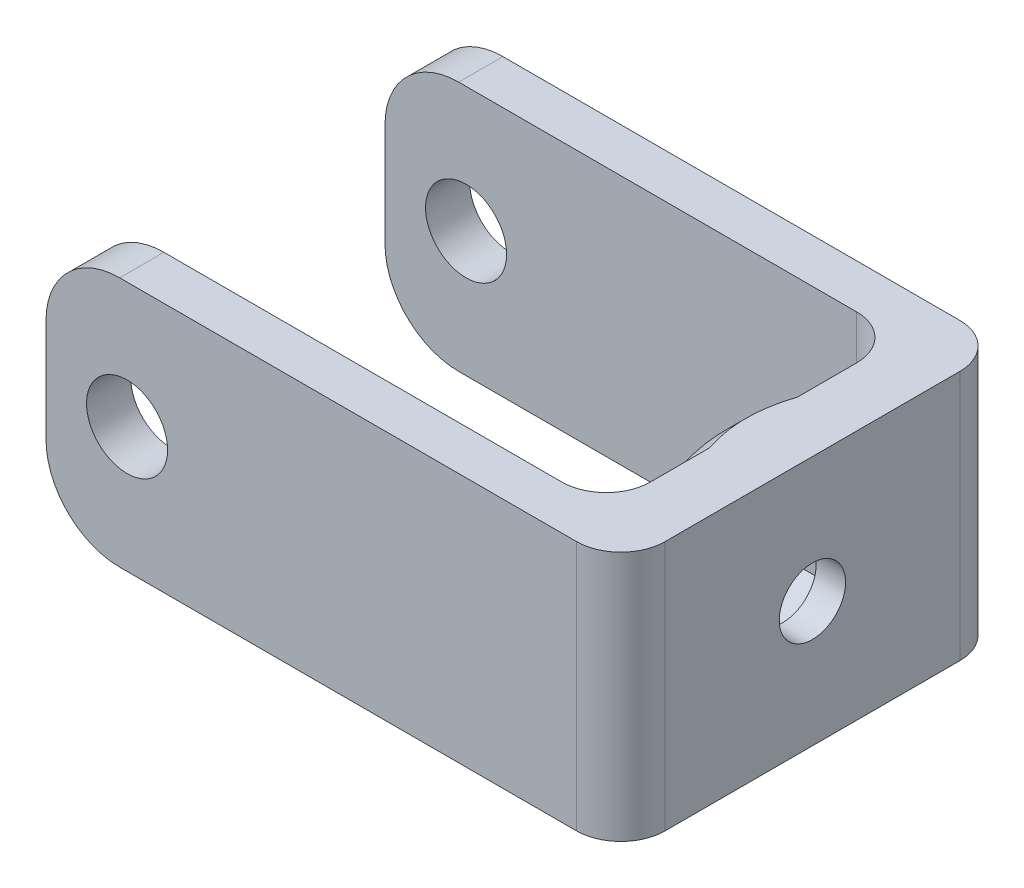
SolidWorks part; units mm, degrees
ref_plane "Front Plane" through (0, 0, 0) normal (0, 0, 1) x (1, 0, 0)
ref_plane "Top Plane" through (0, 0, 0) normal (0, 1, 0) x (1, 0, 0)
ref_plane "Right Plane" through (0, 0, 0) normal (1, 0, 0) x (0, 0, -1)
sketch "Sketch1" plane through (0, 0, 0) normal (1, 0, 0) x (0, 0, -1)
  line L1 (-13, -8.5) -> (13, -8.5)
  line L2 (-13, -8.5) -> (-13, 8.5)
  line L3 (-13, 8.5) -> (13, 8.5)
  line L4 (13, -8.5) -> (13, 8.5)
  line L5 (-13, -8.5) -> (13, 8.5) construction
  line L6 (-13, 8.5) -> (13, -8.5) construction
  point P0 (0, 0)
  dimension "D1" = 17
  dimension "D2" = 26
extrude "Boss-Extrude1" add sketch "Sketch1" along normal blind 4
sketch "Sketch2" plane through (0, 0, 0) normal (-1, 0, 0) x (0, 0, 1)
  line L0 (13, -8.5) -> (-13, -8.5) construction
  line L1 (-13, 8.5) -> (-10, 8.5)
  line L2 (-13, 8.5) -> (-13, -8.5)
  line L3 (-13, -8.5) -> (-10, -8.5)
  line L4 (-10, 8.5) -> (-10, -8.5)
  line L6 (13, 8.5) -> (10, 8.5)
  line L7 (13, 8.5) -> (13, -8.5)
  line L8 (13, -8.5) -> (10, -8.5)
  line L9 (10, 8.5) -> (10, -8.5)
  dimension "D1" = 3
  dimension "D2" = 3
extrude "Boss-Extrude2" add sketch "Sketch2" along normal blind 35
sketch "Sketch3" plane through (0, 0, 13) normal (0, 0, 1) x (1, 0, 0)
  line L1 (-35, -8.5) -> (-35, 8.5) construction
  circle A0 centre (-29.5, 0) radius 2.75
  dimension "D1" = 5.5
  dimension "D2" = 5.5
extrude "Cut-Extrude1" cut sketch "Sketch3" against normal through all
fillet "Fillet1" radius 3 4 edges at (0, 0, 10) (4, 0, 13) (4, 0, -13) (0, 0, -10)
fillet "Fillet2" radius 5 4 edges at (-35, 8.5, -11.5) (-35, -8.5, -11.5) (-35, -8.5, 11.5) (-35, 8.5, 11.5)
sketch "Sketch5" plane through (0, 0, 0) normal (-1, 0, 0) x (0, 0, 1)
  circle A0 centre (0, 0) radius 7
  dimension "D1" = 14
extrude "Boss-Extrude3" add sketch "Sketch5" along normal blind 2
sketch "Sketch7" plane through (4, 0, 0) normal (1, 0, 0) x (0, 0, -1)
  circle A0 centre (0, 0) radius 2.25
  dimension "D1" = 4.5
extrude "Cut-Extrude3" cut sketch "Sketch7" against normal up to next
sketch "Sketch8" plane through (-2, 0, 0) normal (-1, 0, 0) x (0, 0, 1)
  line L1 (0, 4.3301) -> (-3.75, 2.1651)
  line L2 (-3.75, 2.1651) -> (-3.75, -2.1651)
  line L3 (-3.75, -2.1651) -> (0, -4.3301)
  line L4 (0, -4.3301) -> (3.75, -2.1651)
  line L5 (3.75, -2.1651) -> (3.75, 2.1651)
  line L6 (3.75, 2.1651) -> (0, 4.3301)
  circle A0 centre (0, 0) radius 3.75 construction
  dimension "D1" = 7.5
extrude "Cut-Extrude4" cut sketch "Sketch8" against normal blind 4
chamfer "Chamfer1" distance 2 angle 45 2 edges at (0, 7, 0) (0, -7, 0)
